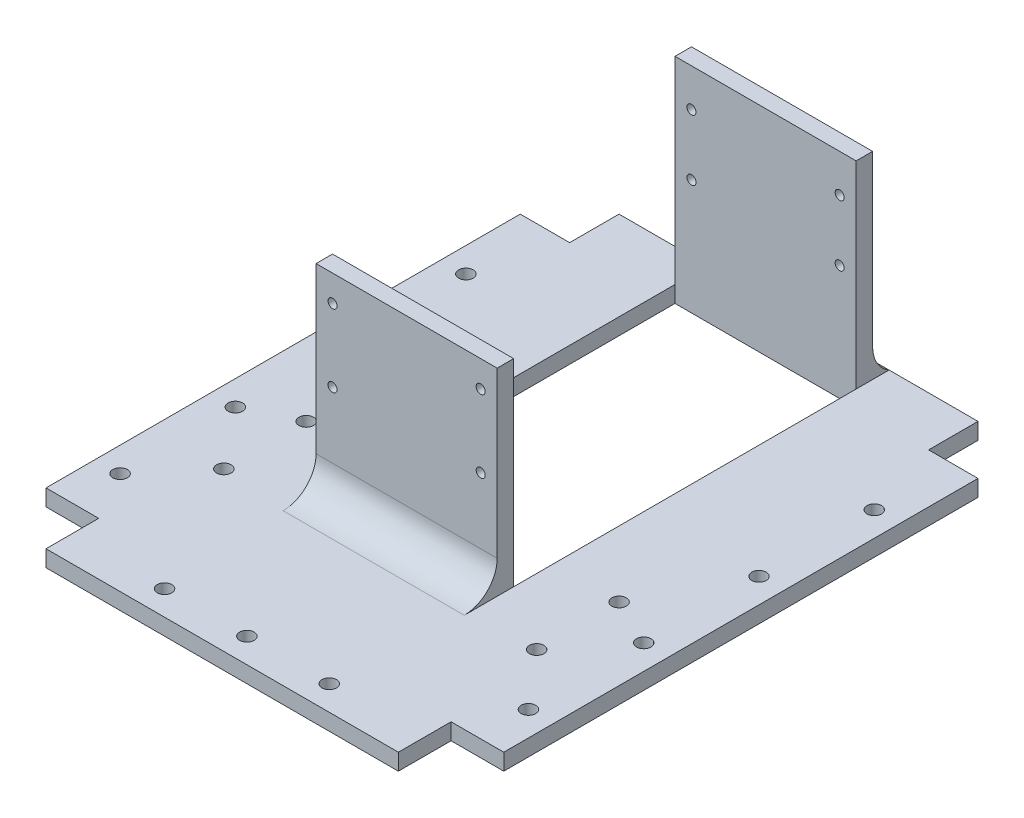
SolidWorks part; units mm, degrees
other "Markup1"
sketch "Sketch7" plane through (-69.5, 3, -80) normal (0, 1, 0) x (1, 0, 0)
sketch "Sketch8" plane through (-69.5, 5, -80) normal (0, 1, 0) x (1, 0, 0)
ref_plane "Front Plane" through (0, 0, 0) normal (0, 0, 1) x (1, 0, 0)
ref_plane "Top Plane" through (0, 0, 0) normal (0, 1, 0) x (1, 0, 0)
ref_plane "Right Plane" through (0, 0, 0) normal (1, 0, 0) x (0, 0, -1)
sketch "Sketch1" plane through (0, 0, 0) normal (0, 1, 0) x (1, 0, 0)
  line L1 (-69.5, 80) -> (69.5, 80)
  line L2 (-69.5, 80) -> (-69.5, -80)
  line L3 (-69.5, -80) -> (69.5, -80)
  line L4 (69.5, 80) -> (69.5, -80)
  line L5 (-69.5, 80) -> (69.5, -80) construction
  line L6 (-69.5, -80) -> (69.5, 80) construction
  point P0 (0, 0)
  dimension "D1" = 160
  dimension "D2" = 139
extrude "Boss-Extrude1" add sketch "Sketch1" along normal blind 5
sketch "Sketch2" plane through (0, 5, 0) normal (0, 1, 0) x (1, 0, 0)
  line L1 (-69.5, -80) -> (-53.5, -80)
  line L2 (-69.5, -80) -> (-69.5, -64)
  line L3 (-69.5, -64) -> (-53.5, -64)
  line L4 (-53.5, -80) -> (-53.5, -64)
  dimension "D1" = 16
  dimension "D2" = 16
extrude "Cut-Extrude1" cut sketch "Sketch2" against normal through all
mirror "Mirror1" about plane through (0, 0, 0) normal (1, 0, 0) of "Cut-Extrude1"
sketch "Sketch3" plane through (0, 5, 0) normal (0, 1, 0) x (1, 0, 0)
  line L0 (0, -2.75) -> (0, 2.75) construction
  line L1 (-53.5, -80) -> (53.5, -80) construction
  circle A0 centre (0, -72.5) radius 2.2
  circle A1 centre (-25, -72.5) radius 2.2
  circle A2 centre (25, -72.5) radius 2.2
  dimension "D1" = 4.4
  dimension "D2" = 4.4
  dimension "D3" = 4.4
  dimension "D4" = 25
  dimension "D5" = 25
  dimension "D6" = 7.5
extrude "Cut-Extrude2" cut sketch "Sketch3" against normal through all
sketch "Sketch4" plane through (0, 5, 0) normal (0, 1, 0) x (1, 0, 0)
  line L0 (-53.5, -64) -> (-69.5, -64) construction
  line L1 (-69.5, 80) -> (-69.5, -64) construction
  circle A0 centre (-62, -49) radius 2.2
  dimension "D3" = 4.4
  dimension "D1" = 15
  dimension "D2" = 7.5
extrude "Cut-Extrude3" cut sketch "Sketch4" against normal through all
pattern_linear "LPattern1" count 4 spacing 35 along (0, 0, -1) of "Cut-Extrude3"
mirror "Mirror2" about plane through (0, 0, 0) normal (1, 0, 0) of "LPattern1", "Cut-Extrude3"
sketch "Sketch5" plane through (0, 5, 0) normal (0, 1, 0) x (1, 0, 0)
  line L0 (0, -2.75) -> (0, 2.75) construction
  line L1 (-53.5, -80) -> (53.5, -80) construction
  circle A0 centre (-47.5, -32) radius 2.2
  circle A1 centre (-47.5, -7) radius 2.2
  dimension "D4" = 4.4
  dimension "D5" = 4.4
  dimension "D1" = 47.5
  dimension "D2" = 47.5
  dimension "D3" = 25
  dimension "D6" = 48
extrude "Cut-Extrude4" cut sketch "Sketch5" against normal through all
mirror "Mirror3" about plane through (0, 0, 0) normal (1, 0, 0) of "Cut-Extrude4"
sketch "Sketch10" plane through (0, 5, 0) normal (0, 1, 0) x (1, 0, 0)
  line L0 (-54.5, 80) -> (54.5, 80)
  line L1 (-54.5, 80) -> (-54.5, 95)
  line L2 (54.5, 80) -> (54.5, 95)
  line L3 (-54.5, 95) -> (54.5, 95)
  line L4 (69.5, 80) -> (-69.5, 80) construction
  line L5 (-69.5, 80) -> (-69.5, -64) construction
  line L6 (69.5, -64) -> (69.5, 80) construction
  dimension "D1" = 15
  dimension "D2" = 15
  dimension "D3" = 15
extrude "Boss-Extrude2" add sketch "Sketch10" against normal up to surface (5 mm away) up to face at (47.5, 0, 34.2)
sketch "Sketch9" plane through (0, 5, 0) normal (0, 1, 0) x (1, 0, 0)
  line L0 (0, -2.75) -> (0, 2.75) construction
  line L1 (-27.5, -19) -> (27.5, -19)
  line L2 (-27.5, -19) -> (-27.5, 85)
  line L3 (-27.5, 85) -> (27.5, 85)
  line L4 (27.5, -19) -> (27.5, 85)
  line L5 (-27.5, -19) -> (27.5, 85) construction
  line L6 (-27.5, 85) -> (27.5, -19) construction
  line L8 (54.5, 95) -> (-54.5, 95) construction
  point P0 (0, 33)
  dimension "D1" = 10
  dimension "D2" = 104
  dimension "D3" = 55
extrude "Cut-Extrude5" cut sketch "Sketch9" against normal through all
sketch "Sketch11" plane through (0, 5, 0) normal (0, 1, 0) x (1, 0, 0)
  line L0 (-27.5, 85) -> (27.5, 85)
  line L1 (-27.5, 85) -> (-27.5, 90)
  line L2 (27.5, 85) -> (27.5, 90)
  line L3 (-27.5, 90) -> (27.5, 90)
  line L4 (-27.5, -19) -> (27.5, -19)
  line L5 (-27.5, -19) -> (-27.5, -24)
  line L6 (27.5, -19) -> (27.5, -24)
  line L7 (-27.5, -24) -> (27.5, -24)
  dimension "D1" = 5
  dimension "D2" = 5
extrude "Boss-Extrude3" add sketch "Sketch11" along normal blind 60
sketch "Sketch12" plane through (0, 0, 24) normal (0, 0, 1) x (1, 0, 0)
  line L0 (-27.5, 5) -> (27.5, 5) construction
  line L1 (0, -35.75) -> (0, 35.75) construction
  circle A0 centre (-22.5, 35) radius 1.375
  circle A2 centre (22.5, 35) radius 1.375
  dimension "D3" = 2.75
  dimension "D1" = 30
  dimension "D2" = 22.5
extrude "Cut-Extrude6" cut sketch "Sketch12" against normal through all
sketch "Sketch13" plane through (0, 0, 24) normal (0, 0, 1) x (1, 0, 0)
  line L0 (0, -35.75) -> (0, 35.75) construction
  circle A0 centre (-22.5, 57) radius 1.375
  circle A1 centre (-22.5, 35) radius 1.375 construction
  circle A2 centre (22.5, 57) radius 1.375
  dimension "D2" = 2.75
  dimension "D1" = 22.5
  dimension "D3" = 22
extrude "Cut-Extrude7" cut sketch "Sketch13" against normal up to next
sketch "Sketch14" plane through (0, 0, -90) normal (0, 0, -1) x (-1, 0, 0)
  line L0 (-22.5, 35) -> (-22.5, 57.1524) construction
  line L1 (0, 35.75) -> (0, -35.75) construction
  circle A0 centre (-22.5, 53.5) radius 1.375
  circle A1 centre (22.5, 53.5) radius 1.375
  dimension "D2" = 2.75
  dimension "D1" = 18.5
extrude "Cut-Extrude8" cut sketch "Sketch14" against normal up to next
fillet "Fillet1" radius 10 1 edges at (0, 5, 24)
fillet "Fillet2" radius 10 1 edges at (0, 5, -90)
equation "\"D3@Sketch3\"=\"D1@Sketch3\""
equation "\"D2@Sketch3\"=\"D1@Sketch3\""
equation "\"D2@Sketch5\"=\"D1@Sketch5\""
